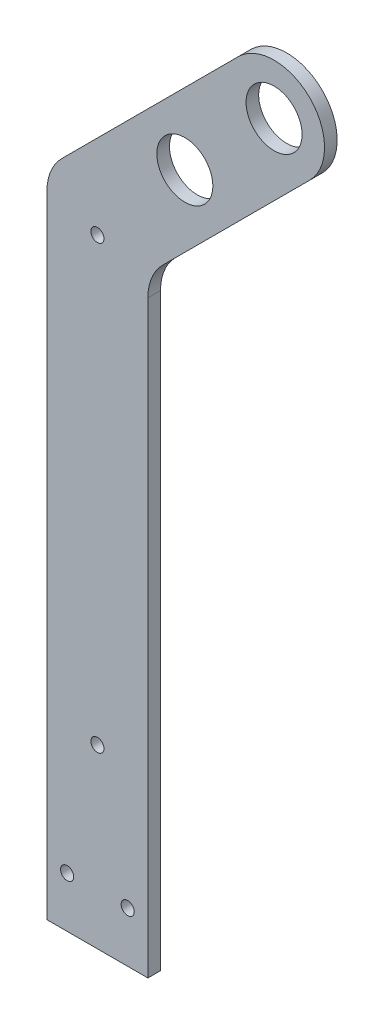
SolidWorks part; units mm, degrees
material "6061 合金"
ref_plane "前视基准面" through (0, 0, 0) normal (0, 0, 1) x (1, 0, 0)
ref_plane "上视基准面" through (0, 0, 0) normal (0, 1, 0) x (1, 0, 0)
ref_plane "右视基准面" through (0, 0, 0) normal (1, 0, 0) x (0, 0, -1)
other "Configuration Table"
sketch "草图1" plane through (0, 0, 0) normal (0, 0, 1) x (1, 0, 0)
  circle A0 centre (0, 0) radius 20
  circle A1 centre (0, 0) radius 11.1
  dimension "D1" = 40
  dimension "D2" = 22.2
extrude "凸台-拉伸1" add sketch "草图1" along normal blind 60 contours A1 | A0 region at (0, 0, 0)
ref_plane "基准面1" through (0, 0, 30) normal (0, 0, 1) x (1, 0, 0)
sketch "草图2" plane through (0, 0, 30) normal (0, 0, 1) x (1, 0, 0)
  line L0 (0, 0) -> (-70, -70) construction
  line L1 (-70, -70) -> (-70, -320) construction
  line L2 (0, -57.3148) -> (0, 49.9409) construction
  line L3 (-56.8582, 0) -> (46.4003, 0) construction
  line L4 (-14.1421, 14.1421) -> (-90, -61.7157)
  line L5 (14.1421, -14.1421) -> (-50, -78.2843)
  line L6 (-90, -61.7157) -> (-90, -320)
  line L7 (-50, -78.2843) -> (-50, -320)
  line L8 (-90, -320) -> (-50, -320)
  circle A2 centre (0, 0) radius 20 construction
  arc A3 (-14.1421, 14.1421) -> (14.1421, -14.1421) centre (0, 0) ccw
  dimension "D1" = 45
  dimension "D2" = 250
  dimension "D3" = 70
  dimension "D4" = 40
  dimension "D5" = 40
extrude "凸台-拉伸2" add sketch "草图2" along normal mid plane 60 contours L7 L8 L6 L4 A3 L5
sketch "草图4" plane through (0, 0, 60) normal (0, 0, 1) x (1, 0, 0)
  line L0 (-90, -61.7157) -> (-90, -320) construction
  line L1 (-90, -290) -> (-50, -290)
  line L2 (-90, -290) -> (-90, -350)
  line L4 (-50, -290) -> (-50, -350)
  line L5 (-50, -78.2843) -> (-50, -320) construction
  line L6 (-90, -320) -> (-50, -320) construction
  arc A0 (-90, -350) -> (-50, -350) centre (-70, -350) ccw
  circle A1 centre (-70, -350) radius 11
  dimension "D3" = 22
  dimension "D1" = 30
  dimension "D2" = 30
extrude "凸台-拉伸3" add sketch "草图4" along normal blind 5
mirror "镜向1" about plane through (0, 0, 30) normal (0, 0, 1) of "凸台-拉伸3"
sketch "草图5" plane through (0, 0, 0) normal (0, 1, 0) x (1, 0, 0)
  line L0 (0, 0) -> (0, -78.0582) construction
ref_plane "基准面2" through (-70, 0, 0) normal (-1, 0, 0) x (0, 0, 1)
sketch "草图7" plane through (-70, 0, 0) normal (-1, 0, 0) x (0, 0, 1)
  line L0 (-34.1239, -350) -> (109.535, -350) construction
sketch "草图8" plane through (0, 0, 60) normal (0, 0, 1) x (1, 0, 0)
  line L0 (0, 0) -> (-70, -70) construction
  circle A0 centre (-35.3553, -35.3553) radius 11.1
  dimension "D1" = 22.2
  dimension "D2" = 50
extrude "切除-拉伸1" cut sketch "草图8" against normal blind 100
fillet "圆角4" radius 20 2 edges at (-90, -61.7157, 30) (-50, -78.2843, 30)
fillet "圆角1" [suppressed] radius 50
fillet "圆角2" [suppressed] radius 3
sketch "草图9" plane through (0, 0, 65) normal (0, 0, 1) x (1, 0, 0)
  circle A0 centre (-70, -350) radius 13
  dimension "D1" = 26
extrude "切除-拉伸2" [suppressed] cut sketch "草图9" against normal blind 0.75
sketch "草图10" plane through (0, 0, -5) normal (0, 0, -1) x (-1, 0, 0)
  circle A0 centre (70, -350) radius 13
  dimension "D1" = 26
extrude "切除-拉伸3" [suppressed] cut sketch "草图10" against normal blind 0.75 contours A0
sketch "草图11" plane through (-90, 0, 0) normal (-1, 0, 0) x (0, 0, 1)
  circle A0 centre (48.5, -118.9949) radius 2.75
  circle A1 centre (48.5, -183.9949) radius 2.75
  circle A2 centre (48.5, -248.9949) radius 2.75
  circle A3 centre (11.5, -248.9949) radius 2.75
  circle A4 centre (11.5, -183.9949) radius 2.75
  circle A5 centre (11.5, -118.9949) radius 2.75
  dimension "D1" = 5.5
extrude "切除-拉伸4" [suppressed] cut sketch "草图11" against normal through all contours A1 | A2 | A0 | A3 | A4 | A5
sketch "草图12" [suppressed] plane through (-90, 0, 0) normal (-1, 0, 0) x (0, 0, 1)
  line L0 (30, -62.0134) -> (30, -339.6946) construction
  line L1 (10, -128.9949) -> (50, -128.9949)
  line L2 (10, -128.9949) -> (10, -173.9949)
  line L3 (10, -173.9949) -> (50, -173.9949)
  line L4 (50, -128.9949) -> (50, -173.9949)
  line L5 (10, -193.9949) -> (50, -193.9949)
  line L6 (10, -193.9949) -> (10, -238.9949)
  line L7 (10, -238.9949) -> (50, -238.9949)
  line L8 (50, -193.9949) -> (50, -238.9949)
  line L9 (10, -258.9949) -> (50, -258.9949)
  line L10 (10, -258.9949) -> (10, -290)
  line L11 (10, -290) -> (50, -290)
  line L12 (50, -258.9949) -> (50, -290)
  line L13 (19.5, -173.9949) -> (40.5, -173.9949)
  line L14 (19.5, -173.9949) -> (19.5, -193.9949)
  line L15 (19.5, -193.9949) -> (40.5, -193.9949)
  line L16 (40.5, -173.9949) -> (40.5, -193.9949)
  line L17 (19.5, -238.9949) -> (40.5, -238.9949)
  line L18 (19.5, -238.9949) -> (19.5, -258.9949)
  line L19 (19.5, -258.9949) -> (40.5, -258.9949)
  line L20 (40.5, -238.9949) -> (40.5, -258.9949)
  line L21 (60, -82.4264) -> (60, -290) construction
  line L22 (0, -290) -> (0, -82.4264) construction
  line L23 (57, -320) -> (3, -320) construction
  circle A0 centre (48.5, -118.9949) radius 2.75 construction
  circle A1 centre (48.5, -183.9949) radius 2.75 construction
  circle A2 centre (48.5, -248.9949) radius 2.75 construction
  dimension "D1" = 10
  dimension "D2" = 10
  dimension "D3" = 10
  dimension "D4" = 8
  dimension "D5" = 10
  dimension "D6" = 10
  dimension "D7" = 10
  dimension "D8" = 30
extrude "减重" [suppressed] cut sketch "草图12" against normal through all contours L0 L1 L2 L3 | L15 L0 L17 L7 L8 L5 | L0 L5 L6 L7 | L19 L0 L11 L12 L9 | L0 L9 L10 L11 | L1 L0 L13 L3 L4
fillet "圆角3" [suppressed] radius 3
sketch "草图13" plane through (0, 0, 60) normal (0, 0, 1) x (1, 0, 0)
  circle A0 centre (0, 0) radius 13
  circle A1 centre (-35.3553, -35.3553) radius 13
  dimension "D1" = 26
  dimension "D2" = 26
extrude "切除-拉伸6" [suppressed] cut sketch "草图13" against normal blind 1.75
sketch "草图14" plane through (0, 0, 0) normal (0, 0, -1) x (-1, 0, 0)
  circle A0 centre (0, 0) radius 13
  circle A1 centre (35.3553, -35.3553) radius 13
  dimension "D1" = 26
  dimension "D2" = 26
extrude "切除-拉伸7" [suppressed] cut sketch "草图14" against normal blind 1.75
sketch "草图15" [suppressed] plane through (0, 0, 0) normal (0, 0, -1) x (-1, 0, 0)
  line L0 (0, 0) -> (70, -350) construction
  line L1 (56.2719, -67.2005) -> (60.1942, -86.8121) construction
  line L2 (70, -350) -> (204.3541, -323.1292) construction
  circle A0 centre (56.2719, -67.2005) radius 2.75
  circle A1 centre (75.2172, -73.6095) radius 2.75
  circle A2 centre (60.1942, -86.8121) radius 2.75
  dimension "D1" = 5.5
  dimension "D2" = 20
  dimension "D3" = 20
  dimension "D4" = 20
  dimension "D5" = 42
  dimension "D6" = 270
extrude "切除-拉伸8" [suppressed] cut sketch "草图15" against normal through all contours A2 | A0 | A1
ref_plane "小腿主干连杆面" through (0, 0, 0) normal (0.9806, -0.1961, 0) x (0, 0, -1)
ref_plane "小腿主干对称面" through (0, 0, 30) normal (0, 0, -1) x (-1, 0, 0)
sketch "草图16" plane through (0, 0, 60) normal (0, 0, 1) x (1, 0, 0)
  line L0 (0, 0) -> (-70, -350)
  line L1 (-35.3553, -35.3553) -> (0, 0)
sketch "草图17" plane through (0, 0, 60) normal (0, 0, 1) x (1, 0, 0)
  line L0 (0, 0) -> (-70, -350) construction
  line L1 (118.6974, 32.5948) -> (32.9122, -396.3312) construction
  line L2 (92.7764, -97.0102) -> (20.2919, -82.5133)
  line L3 (73.1648, -195.0683) -> (0.6803, -180.5713)
  circle A0 centre (20.2919, -82.5133) radius 46
  circle A1 centre (0.6803, -180.5713) radius 46
  dimension "D3" = 92
  dimension "D4" = 92
  dimension "D1" = 110
  dimension "D2" = 73.92
  dimension "D5" = 180
  dimension "D6" = 280
sketch "草图18" plane through (0, 0, 60) normal (0, 0, 1) x (1, 0, 0)
  line L1 (14.1421, -14.1421) -> (-44.1421, -72.4264) construction
  line L3 (14.1421, -14.1421) -> (-44.1421, -72.4264)
  line L4 (15.4873, -12.6548) -> (52.8188, -49.9864)
  line L5 (-50, -128.5133) -> (20.2919, -128.5133)
  line L10 (-90, -290) -> (-50, -290)
  line L11 (-50, -290) -> (-50, -86.5685)
  line L12 (-44.1421, -72.4264) -> (14.1421, -14.1421)
  line L13 (-14.1421, 14.1421) -> (-84.1421, -55.8579)
  line L14 (-90, -70) -> (-90, -290)
  line L16 (-50, -128.5133) -> (-50, -86.5685)
  line L17 (-44.1421, -72.4264) -> (14.1421, -14.1421)
  circle A0 centre (20.2919, -82.5133) radius 46 construction
  arc A1 (14.1421, -14.1421) -> (-14.1421, 14.1421) centre (0, 0) ccw construction
  arc A2 (14.1421, -14.1421) -> (-14.1421, 14.1421) centre (0, 0) ccw
  arc A3 (14.1421, -14.1421) -> (15.4873, -12.6548) centre (0, 0) ccw
  arc A4 (20.2919, -128.5133) -> (52.8188, -49.9864) centre (20.2919, -82.5133) ccw
  circle A5 centre (20.2919, -82.5133) radius 35
  arc A9 (-84.1421, -55.8579) -> (-90, -70) centre (-70, -70) ccw
  arc A10 (-84.1421, -55.8579) -> (-90, -70) centre (-70, -70) ccw
  arc A11 (-44.1421, -72.4264) -> (-50, -86.5685) centre (-30, -86.5685) ccw
  arc A12 (-44.1421, -72.4264) -> (-50, -86.5685) centre (-30, -86.5685) ccw
  line M14 (-50, -290) -> (-50, -86.5685)
  line M15 (-44.1421, -72.4264) -> (14.1421, -14.1421)
  arc M16 (14.1421, -14.1421) -> (-14.1421, 14.1421) centre (0, 0) ccw
  arc M22 (-50, -86.5685) -> (-44.1421, -72.4264) centre (-30, -86.5685) cw
  dimension "D2" = 70
  dimension "D1" = 0
extrude "凸台-拉伸4" add sketch "草图18" against normal blind 5 from offset 25 contours L5 A4 L4 A5 M16 M15 M22 M14 region at (16.0508, -14.5165, 60) offset against normal yes
sketch "草图19" plane through (0, 0, 0) normal (0, 0, -1) x (-1, 0, 0)
  line L0 (50, -86.5685) -> (50, -290) construction
  line L1 (50, -134.5713) -> (50, -226.5713)
  line L2 (-0.6803, -134.5713) -> (50, -134.5713)
  line L3 (-0.6803, -226.5713) -> (50, -226.5713)
  circle A0 centre (-0.6803, -180.5713) radius 46 construction
  arc A1 (-0.6803, -134.5713) -> (-0.6803, -226.5713) centre (-0.6803, -180.5713) ccw
  circle A2 centre (-0.6803, -180.5713) radius 35
  dimension "D1" = 70
extrude "凸台-拉伸5" add sketch "草图19" against normal blind 5 from offset 25 offset against normal yes
fillet "圆角5" radius 10 2 edges at (-50, -226.5713, 27.5) (-50, -128.5133, 32.5)
sketch "草图21" plane through (0, 0, 65) normal (0, 0, 1) x (1, 0, 0)
  line L0 (-70, -350) -> (-70, -6.9331) construction
  circle A0 centre (-70, -75) radius 2.6
  circle A1 centre (-70, -250) radius 2.6
  circle A2 centre (-58, -300) radius 2.6
  circle A3 centre (-82, -300) radius 2.6
  dimension "D1" = 5.2
  dimension "D2" = 12
  dimension "D3" = 50
  dimension "D4" = 100
  dimension "D5" = 175
extrude "切除-拉伸9" cut sketch "草图21" against normal through all both and the other way through all
sketch "草图22" plane through (-90, 0, 0) normal (-1, 0, 0) x (0, 0, 1)
  line L0 (-5, -350) -> (-5, -370) construction
  line L5 (-5, -388.1295) -> (50, -388.1295)
  line L6 (-5, -388.1295) -> (-5, 64.9179)
  line L7 (-5, 64.9179) -> (50, 64.9179)
  line L8 (50, -388.1295) -> (50, 64.9179)
  line L10 (65, -370) -> (55, -370)
  line L11 (65, -370) -> (65, 61.088)
  line L12 (65, 61.088) -> (55, 61.088)
  line L13 (55, -370) -> (55, 61.088)
  dimension "D1" = 10
  dimension "D2" = 5
extrude "切除-拉伸10" cut sketch "草图22" against normal through all both contours L8 L7 L6 L5 | L13 L12 L11 L10
